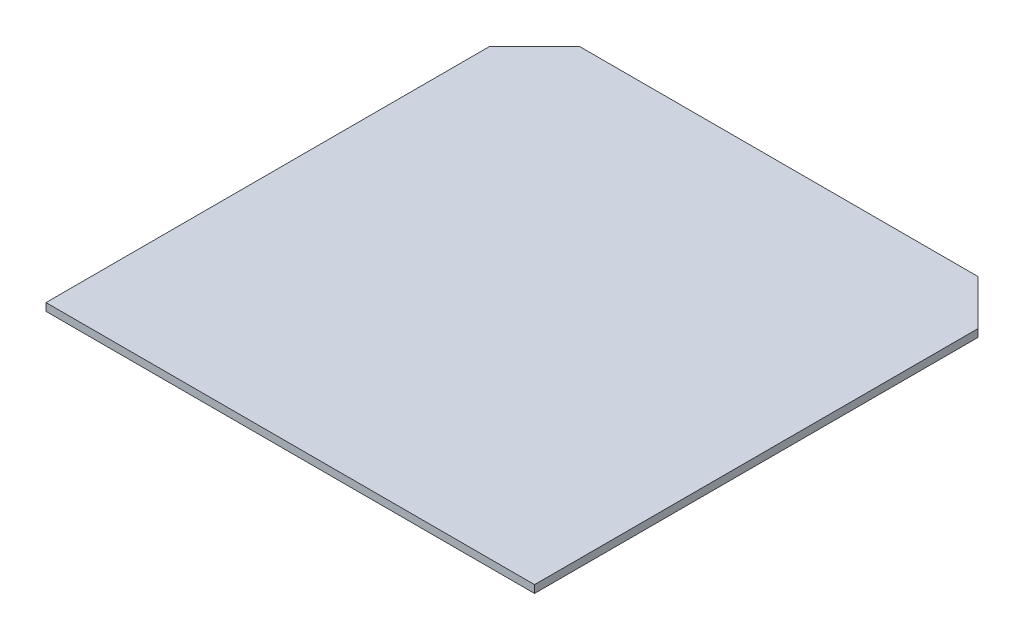
SolidWorks part; units mm, degrees
ref_plane "Front Plane" through (0, 0, 0) normal (0, 0, 1) x (1, 0, 0)
ref_plane "Top Plane" through (0, 0, 0) normal (0, 1, 0) x (1, 0, 0)
ref_plane "Right Plane" through (0, 0, 0) normal (1, 0, 0) x (0, 0, -1)
sketch "Sketch1" plane through (0, 0, 0) normal (0, 1, 0) x (1, 0, 0)
  line L1 (-32.5, -32.5) -> (32.5, -32.5)
  line L2 (-32.5, -32.5) -> (-32.5, 32.5)
  line L3 (-32.5, 32.5) -> (32.5, 32.5)
  line L4 (32.5, -32.5) -> (32.5, 32.5)
  line L5 (-32.5, -32.5) -> (32.5, 32.5) construction
  line L6 (-32.5, 32.5) -> (32.5, -32.5) construction
  point P0 (0, 0)
  dimension "D1" = 65
  dimension "D2" = 65
extrude "Boss-Extrude1" add sketch "Sketch1" along normal blind 1.02
fillet "Chamfer5" radius 6 1 edges at (-32.5, 0.51, -32.5) type face fillet profile chamfer first side face at (0, 0.51, -32.5) second side face at (-32.5, 0.51, 0)
fillet "Chamfer6" radius 6 1 edges at (32.5, 0.51, -32.5) type face fillet profile chamfer first side face at (32.5, 0.51, 0) second side face at (3, 0.51, -32.5)
